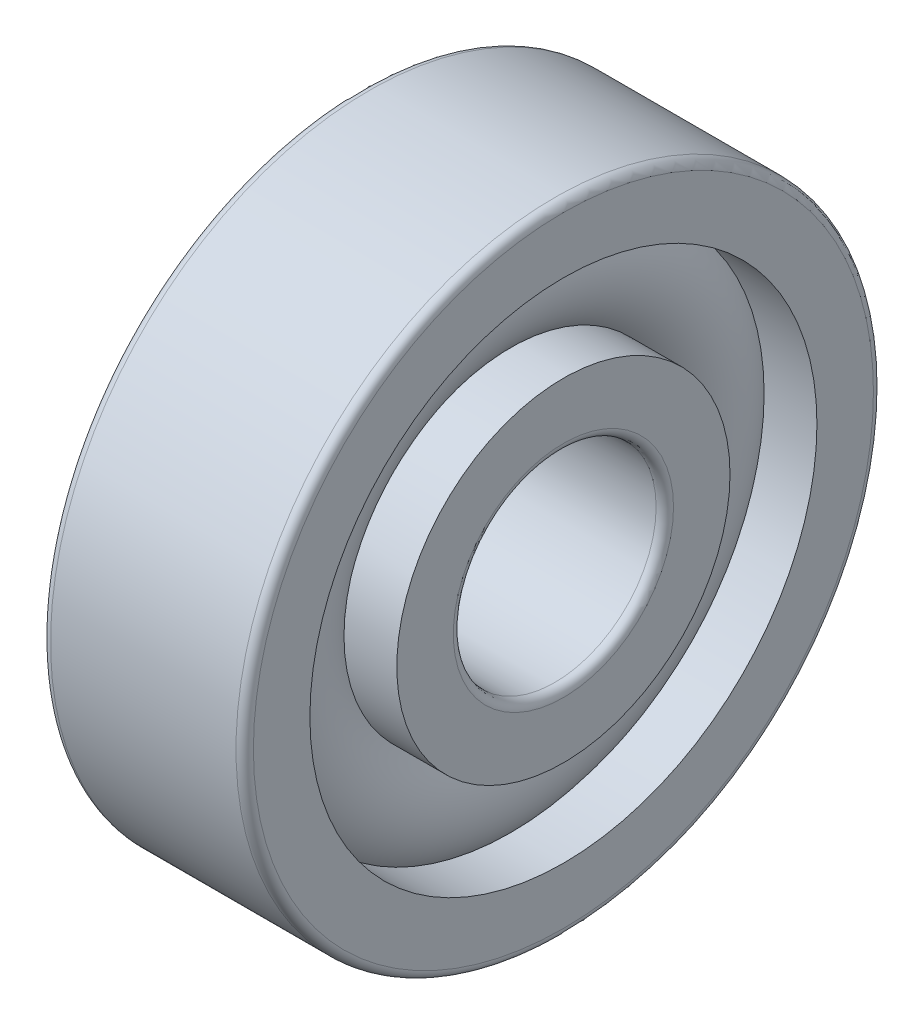
SolidWorks part; units mm, degrees
ref_plane "Plane1" through (0, 0, 0) normal (0, 0, 1) x (1, 0, 0)
ref_plane "Plane2" through (0, 0, 0) normal (0, 1, 0) x (1, 0, 0)
ref_plane "Plane3" through (0, 0, 0) normal (1, 0, 0) x (0, 0, -1)
sketch "Clipboard" plane through (0, 0, 0) normal (0, 0, 1) x (1, 0, 0)
  line L0 (-10, 0) -> (10, 0) construction
  line L1 (0, 0) -> (22.3471, -0.7804)
  line L2 (0, 0) -> (7.2456, 0.253)
  line L3 (0, 0) -> (22.3471, -0.7804)
  line L4 (0, 0) -> (-22.3573, -0.3902)
  dimension "BallCLRad" = 7.25
sketch "CagSpiSke" plane through (0, 0, 0) normal (0, 0, 1) x (1, 0, 0)
  line L0 (0.225, 6.875) -> (0.225, 7.625)
  line L1 (0.225, 7.625) -> (-0.225, 7.625)
  line L2 (-0.225, 7.625) -> (-0.225, 6.875)
  line L3 (-0.225, 6.875) -> (0.225, 6.875)
  line L4 (-20.6375, 0) -> (20.6375, 0) construction
  line L5 (0, 0) -> (0, 23.7692) construction
  dimension "OD" = 15.25
  dimension "ID" = 13.75
revolve "CageSpine" add sketch "CagSpiSke" angle 0.001 about L4 reverse direction yes
ref_axis "Axis1" through (-50, 0, 0) along (1, 0, 0)
sketch "CagBalSke" plane through (0, 0, 0) normal (0, 0, 1) x (1, 0, 0)
  line L0 (-2.475, 7.25) -> (2.475, 7.25)
  line L1 (-1.905, 7.25) -> (1.905, 7.25) construction
  line L2 (-10, 0) -> (10, 0) construction
  line L3 (0, 0) -> (0, 24) construction
  arc A0 (2.475, 7.25) -> (-2.475, 7.25) centre (0, 7.25) cw
  dimension "BallCLRad" = 7.25
revolve "CageBall" [suppressed] add sketch "CagBalSke" angle 360 about L1 reverse direction yes
pattern_circular "CageBalls" [suppressed] count 2 every 180 about axis through (-50, 0, 0) along (1, 0, 0)
sketch "CagTrmODSke" plane through (0, 0, 0) normal (0, 0, 1) x (1, 0, 0)
  line L0 (2.476, 7.625) -> (2.476, 9.726)
  line L1 (2.476, 9.726) -> (-2.476, 9.726)
  line L2 (-2.476, 9.726) -> (-2.476, 7.625)
  line L3 (-2.476, 7.625) -> (2.476, 7.625)
  line L4 (-20.6375, 0) -> (20.6375, 0) construction
  line L5 (0, 0) -> (0, 25) construction
  dimension "Width" = 4.952
  dimension "ID" = 15.25
  dimension "OD" = 19.452
revolve "CageTrimOD" [suppressed] cut sketch "CagTrmODSke" angle 360 about L4 reverse direction yes
sketch "CagTrmIDSke" plane through (0, 0, 0) normal (0, 0, 1) x (1, 0, 0)
  line L0 (2.476, 4.776) -> (2.476, 6.875)
  line L1 (2.476, 6.875) -> (-2.476, 6.875)
  line L2 (-2.476, 6.875) -> (-2.476, 4.776)
  line L3 (-2.476, 4.776) -> (2.476, 4.776)
  line L4 (-20.6375, 0) -> (20.6375, 0) construction
  line L5 (0, 0) -> (0, 25) construction
  dimension "Width" = 4.952
  dimension "ID" = 9.552
  dimension "OD" = 13.75
revolve "CageTrimID" [suppressed] cut sketch "CagTrmIDSke" angle 360 about L4 reverse direction yes
sketch "BalSimSke" plane through (0, 0, 0) normal (0, 0, 1) x (1, 0, 0)
  line L0 (-10, 0) -> (10, 0) construction
  line L1 (-10, 7.25) -> (10, 7.25) construction
  line L2 (0, 0) -> (0, 23) construction
  circle A0 centre (0, 7.25) radius 2.25
  dimension "BallCLRad" = 7.25
  dimension "Ball_diameter" = 4.5
revolve "BallsSimplified" add sketch "BalSimSke" angle 360 about L0
sketch "BalDetSke" plane through (0, 0, 0) normal (0, 0, 1) x (1, 0, 0)
  line L0 (-2.25, 7.25) -> (2.25, 7.25)
  line L1 (-1.905, 7.25) -> (1.905, 7.25) construction
  line L2 (0, 0) -> (0, 25) construction
  arc A0 (2.25, 7.25) -> (-2.25, 7.25) centre (0, 7.25) cw
  dimension "BallCLRad" = 7.25
  dimension "Ball_diameter" = 4.5
revolve "BallDetailed" [suppressed] add sketch "BalDetSke" angle 360 about L1 reverse direction yes
sketch "InnRacSke" plane through (0, 0, 0) normal (0, 0, 1) x (1, 0, 0)
  line L0 (-1.6434, 5.75) -> (-3.5, 5.75)
  line L1 (-3.5, 5.75) -> (-3.5, 3.8)
  line L2 (-3.2, 3.5) -> (3.2, 3.5)
  line L3 (3.5, 3.8) -> (3.5, 5.75)
  line L4 (3.5, 5.75) -> (1.6434, 5.75)
  line L5 (-20.6375, 0) -> (20.6375, 0) construction
  line L6 (0, 0) -> (0, 30) construction
  arc A0 (-3.5, 3.8) -> (-3.2, 3.5) centre (-3.2, 3.8) ccw
  arc A1 (3.2, 3.5) -> (3.5, 3.8) centre (3.2, 3.8) ccw
  arc A2 (1.6434, 5.75) -> (-1.6434, 5.75) centre (0, 7.25) cw
  dimension "BallCLRad" = 7.25
  dimension "Fillet_radius" = 0.3
  dimension "Ball_diameter" = 4.45
  dimension "ID" = 7
  dimension "OD" = 11.5
  dimension "Width" = 7
revolve "InnerRace" add sketch "InnRacSke" angle 360 about L5 reverse direction yes
sketch "OutRacSke" plane through (0, 0, 0) normal (0, 0, 1) x (1, 0, 0)
  line L0 (-1.6434, 8.75) -> (-3.5, 8.75)
  line L1 (-3.5, 8.75) -> (-3.5, 10.7)
  line L2 (-3.2, 11) -> (3.2, 11)
  line L3 (3.5, 10.7) -> (3.5, 8.75)
  line L4 (3.5, 8.75) -> (1.6434, 8.75)
  line L5 (-20.6375, 0) -> (20.6375, 0) construction
  line L6 (0, 0) -> (0, 30) construction
  arc A0 (-3.5, 10.7) -> (-3.2, 11) centre (-3.2, 10.7) cw
  arc A1 (3.2, 11) -> (3.5, 10.7) centre (3.2, 10.7) cw
  arc A2 (1.6434, 8.75) -> (-1.6434, 8.75) centre (0, 7.25) ccw
  dimension "BallCLRad" = 7.25
  dimension "Fillet_radius" = 0.3
  dimension "Ball_diameter" = 4.45
  dimension "Width" = 7
revolve "OuterRace" add sketch "OutRacSke" angle 360 about L5 reverse direction yes
pattern_circular "BallsDetailed" [suppressed] count 2 every 180 about axis through (-50, 0, 0) along (1, 0, 0)
equation "\"BallCLRad@Clipboard\" = ( \"OD@OutRacSke\" + \"ID@InnRacSke\" ) / 4"
equation "\"BallCLRad@BalSimSke\" = \"BallCLRad@Clipboard\""
equation "\"BallCLRad@BalDetSke\" = \"BallCLRad@Clipboard\""
equation "\"BallCLRad@InnRacSke\" = \"BallCLRad@Clipboard\""
equation "\"BallCLRad@OutRacSke\" = \"BallCLRad@Clipboard\""
equation "\"Ball_diameter@InnRacSke\" = \"Ball_diameter@BalDetSke\" - 0.05"
equation "\"Ball_diameter@OutRacSke\" = \"Ball_diameter@BalDetSke\" - 0.05"
equation "\"Ball_diameter@BalSimSke\" = \"Ball_diameter@BalDetSke\""
equation "\"Width@OutRacSke\" = \"Width@InnRacSke\""
equation "\"Fillet_radius@OutRacSke\" = \"Fillet_radius@InnRacSke\""
equation "\"Max_count@Clipboard\" = int( 3.14159265 / atn(( \"Ball_diameter@BalDetSke\" / 2) / sqr( \"BallCLRad@Clipboard\"  *  \"BallCLRad@Clipboard\" - ( \"Ball_diameter@BalDetSke\" / 2) *  ( \"Ball_diameter@BalDetSke\" / 2))))"
equation "\"Max_count@Clipboard\" = ((sgn( \"Max_count@Clipboard\" - \"Count@Clipboard\" )-1)*( \"Max_count@Clipboard\" - \"Count@Clipboard\" ))/-2+ \"Count@Clipboard\""
equation "\"Count@BallsDetailed\" = int( \"Show_count@Clipboard\" ) "
equation "\"Count@BallsDetailed\" = ((sgn( \"Count@BallsDetailed\" - \"Max_count@Clipboard\" )-1)*( \"Count@BallsDetailed\" - \"Max_count@Clipboard\" ))/-2+ \"Max_count@Clipboard\""
equation "\"Count@BallsDetailed\" = ((sgn( \"Count@BallsDetailed\" - \"Min_count@Clipboard\" )+1)*( \"Count@BallsDetailed\" - \"Min_count@Clipboard\"))/2 +\"Min_count@Clipboard\""
equation "\"Angle@BallsDetailed\" = 360.0 / \"Max_count@Clipboard\""
equation "\"BallCLRad@CagBalSke\" = \"BallCLRad@Clipboard\""
equation "\"Count@CageBalls\" = \"Count@BallsDetailed\""
equation "\"Angle@CageBalls\" = \"Angle@BallsDetailed\""
equation "\"Angle@CageSpine\" =  \"Angle@CageBalls\" * ( \"Count@CageBalls\" -1 + int( \"Count@CageBalls\" / \"Max_count@Clipboard\" ) )  + 0.001 -  int( \"Count@CageBalls\" / \"Max_count@Clipboard\" ) * 0.001"
equation "\"Angle@CageSpine\" =  \"Angle@CageSpine\" * int( \"Min_count@Clipboard\" / 2) + int(1 / \"Min_count@Clipboard\")  * 0.001"
equation "\"CageWallOD@CagBalSke\" =  \"Ball_diameter@BalDetSke\" * 1.1"
equation "\"Thickness@CagSpiSke\" =  \"Ball_diameter@BalDetSke\" * 0.1"
equation "\"OD@CagTrmODSke\" = \"BallCLRad@Clipboard\" * 2 + \"CageWallOD@CagBalSke\" + 0.002"
equation "\"ID@CagTrmODSke\" = \"BallCLRad@Clipboard\" * 2 + \"Ball_diameter@BalDetSke\" / 6"
equation "\"OD@CagTrmIDSke\" = \"BallCLRad@Clipboard\" * 2 - \"Ball_diameter@BalDetSke\" / 6"
equation "\"ID@CagTrmIDSke\" = \"BallCLRad@Clipboard\" * 2 - \"CageWallOD@CagBalSke\" + 0.002"
equation "\"OD@CagSpiSke\" = \"ID@CagTrmODSke\""
equation "\"ID@CagSpiSke\" = \"OD@CagTrmIDSke\""
equation "\"Width@CagTrmODSke\" = \"CageWallOD@CagBalSke\" + 0.002"
equation "\"Width@CagTrmIDSke\" = \"CageWallOD@CagBalSke\" + 0.002"
